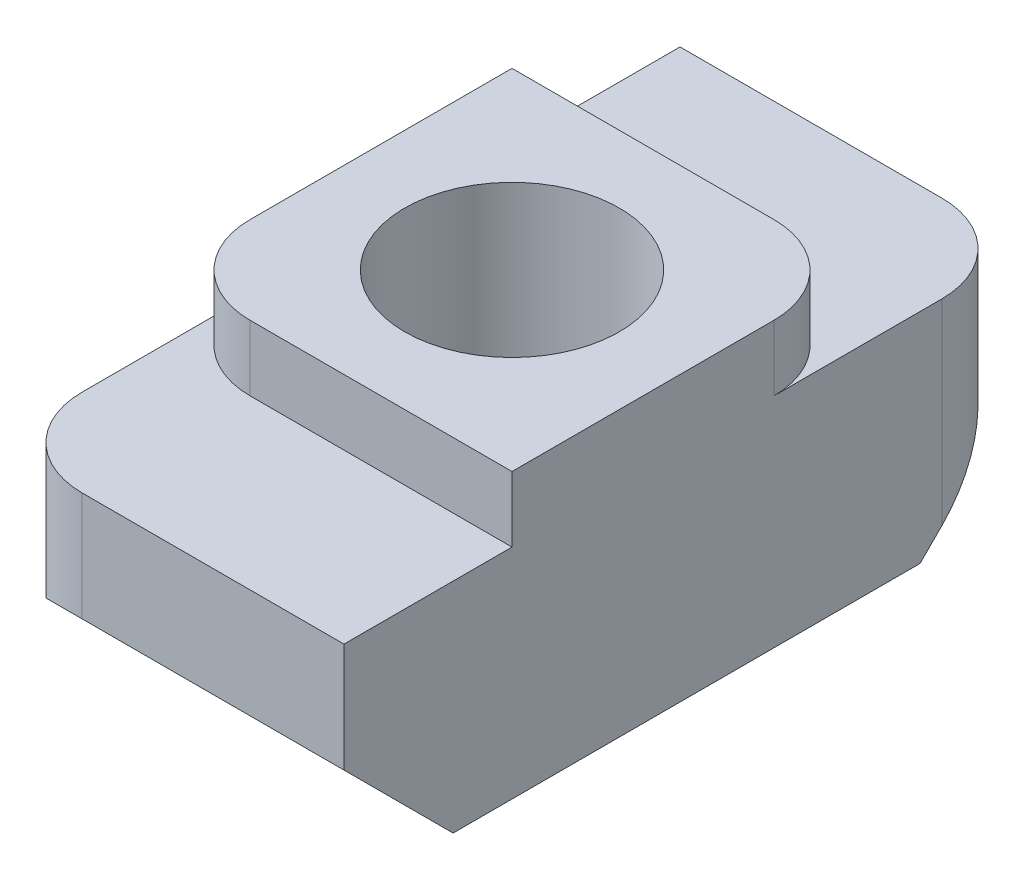
SolidWorks part; units mm, degrees
ref_plane "Front Plane" through (0, 0, 0) normal (0, 0, 1) x (1, 0, 0)
ref_plane "Top Plane" through (0, 0, 0) normal (0, 1, 0) x (1, 0, 0)
ref_plane "Right Plane" through (0, 0, 0) normal (1, 0, 0) x (0, 0, -1)
ref_axis "Axis_X" through (-4.4, 0, 0) along (1, 0, 0)
ref_axis "Axis_Y" through (0, 0.325, 0) along (0, -1, 0)
ref_axis "Axis_Z" through (0, 0, -8.635) along (0, 0, 1)
sketch "Sketch1" plane through (0, 0, 0) normal (1, 0, 0) x (0, 0, -1)
  line L0 (-4, 0) -> (4, 0)
  line L1 (4, 0) -> (4, -1.5)
  line L2 (4, -1.5) -> (7.85, -1.5)
  line L3 (7.85, -1.5) -> (7.85, -4)
  line L4 (7.85, -4) -> (5.35, -6.5)
  line L5 (5.35, -6.5) -> (-5.35, -6.5)
  line L6 (-5.35, -6.5) -> (-7.85, -4)
  line L7 (-7.85, -4) -> (-7.85, -1.5)
  line L8 (-7.85, -1.5) -> (-4, -1.5)
  line L9 (-4, -1.5) -> (-4, 0)
  line L10 (0, 0) -> (0, -6.5) construction
  dimension "FIX_1" = 45
  dimension "C" = 15.7
  dimension "A" = 8
  dimension "T" = 5
  dimension "MSM_1" = 2.5
  dimension "E" = 6.5
extrude "Boss-Extrude1" add sketch "Sketch1" along normal mid plane 8
fillet "Fillet1" radius 2 4 edges at (4, -2.75, -7.85) (-4, -2.75, 7.85) (4, -0.75, -4) (-4, -0.75, 4)
hole_wizard "Tap1" positions "Sketch3" profile "Sketch2" hole size "M3x0.5" standard "JIS" end condition through all
sketch "Sketch3" plane through (0, 0, 0) normal (0, 1, 0) x (1, 0, 0)
  point P0 (0, 0)
sketch "Sketch2" plane through (0, 0, 0) normal (1, 0, 0) x (0, 0, 1)
  line L0 (0, 0) -> (0, 6.5)
  line L1 (0, 6.5) -> (2.4585, 6.5)
  line L2 (2.4585, 6.5) -> (2.4585, 0)
  line L5 (2.4585, 0) -> (0, 0)
  line L11 (0, -6.35) -> (0, 107.95) construction
  dimension "HSD_1" = 4.917
  dimension "Thru Hole Depth" = 6.5
cosmetic thread "Thread1" parameters "M"=6
equation "\"Factor\"= 1.082532"
